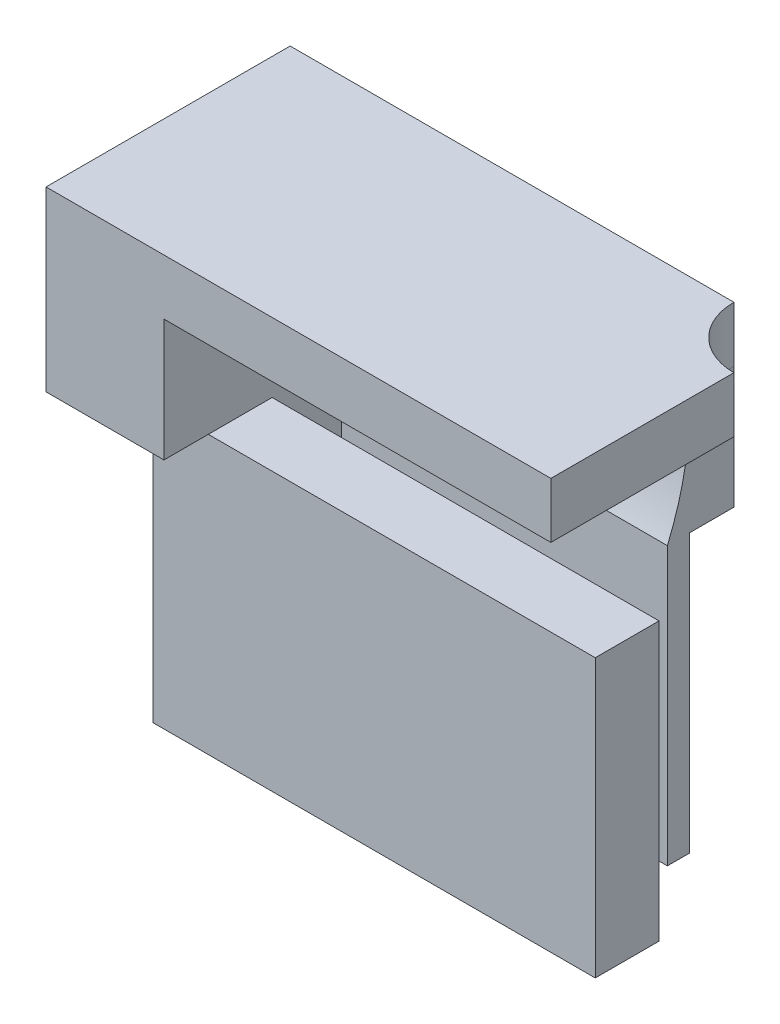
SolidWorks part; units mm, degrees
ref_plane "Front Plane" through (0, 0, 0) normal (0, 0, 1) x (1, 0, 0)
ref_plane "Top Plane" through (0, 0, 0) normal (0, 1, 0) x (1, 0, 0)
ref_plane "Right Plane" through (0, 0, 0) normal (1, 0, 0) x (0, 0, -1)
sketch "Sketch1" plane through (0, 0, 0) normal (0, 1, 0) x (1, 0, 0)
  line L0 (-43.6089, 4.4) -> (-27.6089, 4.4)
  line L5 (-43.6089, 4.4) -> (-43.6089, -4.4)
  line L6 (-43.6089, -4.4) -> (-25.4089, -4.4)
  line L7 (-25.4089, 2.2) -> (-25.4089, -4.4)
  arc A0 (-27.6089, 4.4) -> (-25.4089, 2.2) centre (-25.4089, 4.4) ccw
  dimension "D3" = 2.2
  dimension "D1" = 18.2
  dimension "D2" = 8.8
extrude "Boss-Extrude1" add sketch "Sketch1" along normal blind 2
sketch "Sketch2" plane through (0, 0, 0) normal (0, -1, 0) x (1, 0, 0)
  line L1 (-27.6089, -4.4) -> (-43.6089, -4.4)
  line L2 (-27.6089, -4.4) -> (-27.6089, -2.8)
  line L3 (-27.6089, -2.8) -> (-39.3589, -2.8)
  line L5 (-43.6089, 4.4) -> (-25.4089, 4.4) construction
  line L6 (-43.6089, -4.4) -> (-39.3589, -4.4)
  line L7 (-43.6089, -4.4) -> (-43.6089, 4.4)
  line L8 (-43.6089, 4.4) -> (-39.3589, 4.4)
  line L9 (-39.3589, -2.8) -> (-39.3589, 4.4)
  line M7 (-43.6089, 4.4) -> (-43.6089, -4.4)
  line M8 (-43.6089, -4.4) -> (-27.6089, -4.4)
  line M11 (-25.4089, 4.4) -> (-43.6089, 4.4)
  dimension "D1" = 1.6
  dimension "D2" = 4.25
extrude "Boss-Extrude2" add sketch "Sketch2" along normal blind 4.4 contours L3 L9 L1 L2 M11 M7 M8 region at (-33.4839, 0, -4.2174)
sketch "Sketch3" plane through (0, -4.4, 0) normal (0, -1, 0) x (1, 0, 0)
  line L0 (-41.3589, 2.8) -> (-25.4089, 2.8)
  line L4 (-41.3589, 2.8) -> (-41.3589, -2.8)
  line L11 (-39.3589, 0.5) -> (-25.4089, 0.5)
  line L19 (-25.4089, 4.4) -> (-25.4089, -2.2) construction
  line L20 (-25.4089, 2.8) -> (-25.4089, 0.5)
  line L23 (-27.6089, -2.8) -> (-27.6089, -2)
  line L24 (-43.6089, -4.4) -> (-27.6089, -4.4) construction
  line L27 (-27.6089, -2) -> (-39.3589, -2)
  line L29 (-39.3589, -2) -> (-39.3589, 0.5)
  line L30 (-44.5399, -2.8) -> (-23.5231, -2.8) construction
  line L31 (-27.6089, -2.8) -> (-27.6089, -3.8)
  line L32 (-27.6089, -4.4) -> (-27.6089, -2.8) construction
  line L33 (-27.6089, -3.8) -> (-41.3589, -3.8)
  line L34 (-41.3589, -3.8) -> (-41.3589, -2.8)
  dimension "D1" = 2.4
  dimension "D2" = 2.5
extrude "Boss-Extrude9" add sketch "Sketch3" along normal blind 10
sketch "Sketch6" plane through (0, -14.4, 0) normal (0, -1, 0) x (1, 0, 0)
  line L0 (-41.3589, 2.8) -> (-41.3589, -3.8) construction
  line L1 (-27.6089, -3.8) -> (-41.3589, -3.8)
  line L2 (-27.6089, -3.8) -> (-27.6089, -2.8)
  line L3 (-27.6089, -2.8) -> (-41.3589, -2.8)
  line L4 (-41.3589, -3.8) -> (-41.3589, -2.8)
  dimension "D1" = 1
fillet "Fillet1" radius 10 1 edges at (-33.4839, -4.4, -2.8)
extrude "Cut-Extrude2" cut sketch "Sketch6" against normal blind 10
